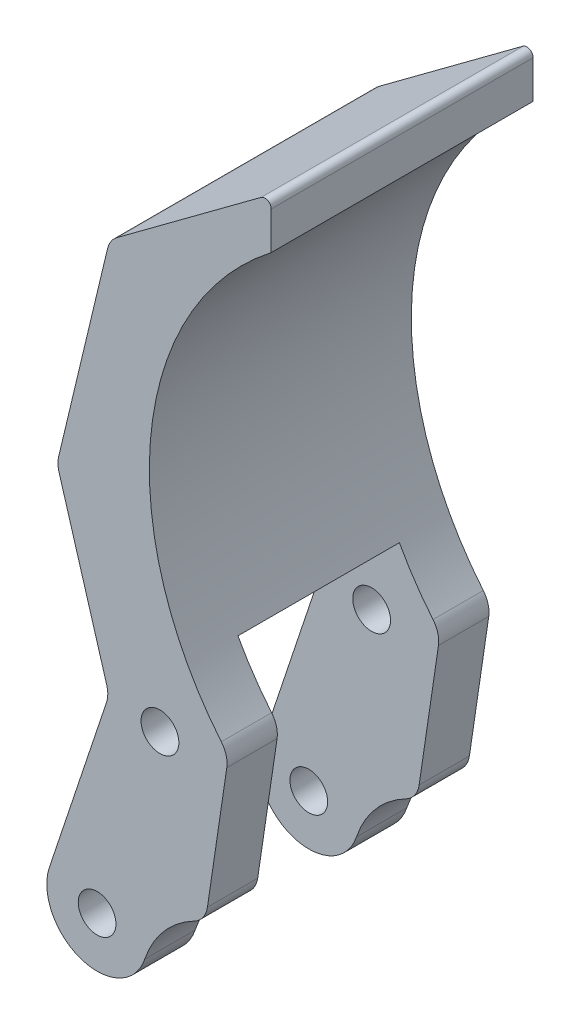
SolidWorks part; units mm, degrees
ref_plane "前视基准面" through (0, 0, 0) normal (0, 0, 1) x (1, 0, 0)
ref_plane "上视基准面" through (0, 0, 0) normal (0, 1, 0) x (1, 0, 0)
ref_plane "右视基准面" through (0, 0, 0) normal (1, 0, 0) x (0, 0, -1)
sketch "草图1" plane through (0, 0, 0) normal (0, 0, 1) x (1, 0, 0)
  line L1 (-44.759, 0) -> (37.6123, 0) construction
  line L2 (0, 0) -> (0, 68.6572) construction
  line L3 (15.4812, 24.7175) -> (6.2807, 1.4721) construction
  line L4 (22.9197, 21.7734) -> (13.7193, -1.4721) construction
  line L5 (22.9952, 24.5104) -> (15.4057, 21.9805) construction
  line L6 (8.8834, 38.4304) -> (10.4236, 28.044) construction
  line L8 (22.9952, 24.5104) -> (18.4512, 38.1424) construction
  line L9 (18.4316, 39.345) -> (22.233, 52.1252) construction
  line L10 (22.2613, 53.1601) -> (18.3728, 69.4382) construction
  line L11 (11.411, 39.3495) -> (2.2105, 16.1041) construction
  line L12 (16.9899, 37.1414) -> (7.7895, 13.8959) construction
  line L13 (17.619, 70.5799) -> (6.1506, 79.0862) construction
  line L14 (5.3527, 78.6846) -> (5.3527, 75.678) construction
  line L15 (-15.4812, 24.7175) -> (-6.2807, 1.4721) construction
  line L16 (-22.9197, 21.7734) -> (-13.7193, -1.4721) construction
  line L17 (-16.9899, 37.1414) -> (-7.7895, 13.8959) construction
  line L18 (-11.411, 39.3495) -> (-2.2105, 16.1041) construction
  line L19 (-8.8834, 38.4304) -> (-10.4236, 28.044)
  line L20 (-22.9952, 24.5104) -> (-18.4512, 38.1424)
  line L25 (-18.4316, 39.345) -> (-22.233, 52.1252)
  line L26 (-5, 15) -> (-10, 0) construction
  line L27 (5, 15) -> (10, 0) construction
  line L28 (14.2005, 38.2455) -> (19.2005, 23.2455) construction
  line L29 (-22.2613, 53.1601) -> (-18.3728, 69.4382)
  line L30 (-17.619, 70.5799) -> (-6.1506, 79.0862)
  line L31 (-5.3527, 78.6846) -> (-5.3527, 75.678)
  line L32 (-9.9581, 55.9149) -> (14.9371, 53.6276) construction
  circle A0 centre (-10, 0) radius 10 construction
  circle A4 centre (0, 55) radius 15 construction
  circle A5 centre (10, 0) radius 4 construction
  circle A6 centre (10, 0) radius 10 construction
  arc A14 (15.4057, 21.9805) -> (10.5848, 26.9564) centre (7.8163, 19.4507) ccw construction
  circle A16 centre (19.2005, 23.2455) radius 1.5 construction
  circle A17 centre (19.2005, 23.2455) radius 4 construction
  circle A18 centre (5, 15) radius 3 construction
  arc A19 (9.3195, 39.9972) -> (5.3527, 75.678) centre (-9.9581, 55.9149) ccw construction
  circle A20 centre (14.2005, 38.2455) radius 3 construction
  circle A21 centre (-10, 0) radius 4 construction
  circle A22 centre (-19.2005, 23.2455) radius 1.5
  arc A23 (-22.9952, 24.5104) -> (-15.4057, 21.9805) centre (-19.2005, 23.2455) ccw
  arc A24 (-15.4057, 21.9805) -> (-11.4848, 26.56) centre (-7.8163, 19.4507) cw
  circle A25 centre (-14.2005, 38.2455) radius 3 construction
  circle A26 centre (-5, 15) radius 3 construction
  circle A28 centre (-14.2005, 38.2455) radius 1.5
  circle A29 centre (-5, 15) radius 1.5 construction
  circle A30 centre (5, 15) radius 1.5 construction
  circle A31 centre (14.2005, 38.2455) radius 1.5 construction
  arc A33 (-11.4848, 26.56) -> (-10.4236, 28.044) centre (-12.4019, 28.3373) ccw
  arc A40 (6.1506, 79.0862) -> (5.3527, 78.6846) centre (5.8527, 78.6846) ccw construction
  arc A41 (11.4848, 26.56) -> (10.4236, 28.044) centre (12.4019, 28.3373) cw construction
  arc A42 (8.8834, 38.4304) -> (9.3195, 39.9972) centre (10.8617, 38.7237) cw construction
  arc A43 (-9.3195, 39.9972) -> (-5.3527, 75.678) centre (9.9581, 55.9149) cw
  arc A44 (18.4512, 38.1424) -> (18.4316, 39.345) centre (20.3486, 38.7748) cw construction
  arc A45 (22.233, 52.1252) -> (22.2613, 53.1601) centre (20.316, 52.6954) ccw construction
  arc A46 (18.3728, 69.4382) -> (17.619, 70.5799) centre (16.4275, 68.9735) ccw construction
  arc A47 (-6.1506, 79.0862) -> (-5.3527, 78.6846) centre (-5.8527, 78.6846) cw
  arc A48 (-8.8834, 38.4304) -> (-9.3195, 39.9972) centre (-10.8617, 38.7237) ccw
  arc A49 (-18.4512, 38.1424) -> (-18.4316, 39.345) centre (-20.3486, 38.7748) ccw
  arc A50 (-22.233, 52.1252) -> (-22.2613, 53.1601) centre (-20.316, 52.6954) cw
  arc A51 (-18.3728, 69.4382) -> (-17.619, 70.5799) centre (-16.4275, 68.9735) cw
  point P93 (5.3527, 79.678)
  point P96 (8.7498, 39.3313)
  point P99 (18.2518, 38.7406)
  point P102 (22.3858, 52.6388)
  point P105 (18.2036, 70.1462)
  point P109 (-5.3527, 79.678)
  point P112 (-8.7498, 39.3313)
  point P115 (-18.2518, 38.7406)
  point P118 (-10.5848, 26.9564)
  point P122 (-22.3858, 52.6388)
  point P125 (-18.2036, 70.1462)
  dimension "D1" = 30
  dimension "D3" = 20
  dimension "D4" = 25
  dimension "D5" = 8
  dimension "D6" = 3
  dimension "D7" = 2
  dimension "D8" = 8
  dimension "D13" = 25
  dimension "D20" = 140
  dimension "D21" = 6
  dimension "D27" = 3
  dimension "D29" = 0.5
  dimension "D28" = 16
  dimension "D30" = 2
  dimension "D31" = 55
  dimension "D14" = 4
  dimension "D12" = 10.5
  dimension "D18" = 150
  dimension "D10" = 0.5
  dimension "D26" = 2
  dimension "D9" = 11
  dimension "D11" = 15
  dimension "D15" = 10
  dimension "D16" = 145
  dimension "D17" = 14.5
  dimension "D19" = 18
  dimension "D22" = 5
  dimension "D23" = 15
  dimension "D24" = 25
  dimension "D25" = 4
extrude "凸台-拉伸1" add sketch "草图1" along normal blind 4
ref_plane "基准面1" through (0, 0, 0) normal (0, 0, -1) x (-1, 0, 0)
sketch "草图9" plane through (0, 0, 0) normal (0, 0, -1) x (-1, 0, 0)
  line L0 (18.4316, 39.345) -> (11.9955, 43.955)
  line L6 (8.8834, 38.4304) -> (10.4236, 28.044)
  line L7 (22.9952, 24.5104) -> (18.4512, 38.1424)
  line L8 (18.4316, 39.345) -> (22.233, 52.1252)
  line L9 (22.2613, 53.1601) -> (18.3728, 69.4382)
  line L10 (17.619, 70.5799) -> (6.1506, 79.0862)
  line L11 (5.3527, 78.6846) -> (5.3527, 75.678)
  line L14 (18.4316, 39.345) -> (22.233, 52.1252)
  line L15 (22.2613, 53.1601) -> (18.3728, 69.4382)
  line L16 (17.619, 70.5799) -> (6.1506, 79.0862)
  line L17 (5.3527, 78.6846) -> (5.3527, 75.678)
  arc A0 (5.3527, 75.678) -> (11.9955, 43.955) centre (-9.9581, 55.9149) cw
  arc A9 (9.3195, 39.9972) -> (5.3527, 75.678) centre (-9.9581, 55.9149) ccw
  arc A10 (9.3195, 39.9972) -> (8.8834, 38.4304) centre (10.8617, 38.7237) ccw
  arc A11 (10.4236, 28.044) -> (11.4848, 26.56) centre (12.4019, 28.3373) ccw
  arc A12 (15.4057, 21.9805) -> (11.4848, 26.56) centre (7.8163, 19.4507) ccw
  arc A13 (15.4057, 21.9805) -> (22.9952, 24.5104) centre (19.2005, 23.2455) ccw
  arc A14 (18.4316, 39.345) -> (18.4512, 38.1424) centre (20.3486, 38.7748) ccw
  arc A15 (22.233, 52.1252) -> (22.2613, 53.1601) centre (20.316, 52.6954) ccw
  arc A16 (18.3728, 69.4382) -> (17.619, 70.5799) centre (16.4275, 68.9735) ccw
  arc A17 (6.1506, 79.0862) -> (5.3527, 78.6846) centre (5.8527, 78.6846) ccw
  arc A24 (22.233, 52.1252) -> (22.2613, 53.1601) centre (20.316, 52.6954) ccw
  arc A25 (18.3728, 69.4382) -> (17.619, 70.5799) centre (16.4275, 68.9735) ccw
  arc A26 (6.1506, 79.0862) -> (5.3527, 78.6846) centre (5.8527, 78.6846) ccw
  dimension "D1" = 0
extrude "凸台-拉伸2" add sketch "草图9" against normal blind 20.84
ref_plane "基准面2" through (0, 0, 20.84) normal (0, 0, 1) x (1, 0, 0)
sketch "草图13" plane through (0, 0, 20.84) normal (0, 0, 1) x (1, 0, 0)
  line L3 (-11.9955, 43.955) -> (-18.4316, 39.345)
  line L4 (-18.4512, 38.1424) -> (-22.9952, 24.5104)
  line L5 (-10.4236, 28.044) -> (-8.8834, 38.4304)
  line L6 (-11.9955, 43.955) -> (-18.4316, 39.345)
  line L7 (-18.4512, 38.1424) -> (-22.9952, 24.5104)
  line L8 (-10.4236, 28.044) -> (-8.8834, 38.4304)
  arc A6 (-11.9955, 43.955) -> (-9.3195, 39.9972) centre (9.9581, 55.9149) ccw
  arc A7 (-18.4512, 38.1424) -> (-18.4316, 39.345) centre (-20.3486, 38.7748) ccw
  arc A8 (-22.9952, 24.5104) -> (-15.4057, 21.9805) centre (-19.2005, 23.2455) ccw
  arc A9 (-11.4848, 26.56) -> (-15.4057, 21.9805) centre (-7.8163, 19.4507) ccw
  arc A10 (-11.4848, 26.56) -> (-10.4236, 28.044) centre (-12.4019, 28.3373) ccw
  arc A11 (-8.8834, 38.4304) -> (-9.3195, 39.9972) centre (-10.8617, 38.7237) ccw
  arc A12 (-11.9955, 43.955) -> (-9.3195, 39.9972) centre (9.9581, 55.9149) ccw
  arc A13 (-18.4512, 38.1424) -> (-18.4316, 39.345) centre (-20.3486, 38.7748) ccw
  arc A14 (-22.9952, 24.5104) -> (-15.4057, 21.9805) centre (-19.2005, 23.2455) ccw
  arc A15 (-11.4848, 26.56) -> (-15.4057, 21.9805) centre (-7.8163, 19.4507) ccw
  arc A16 (-11.4848, 26.56) -> (-10.4236, 28.044) centre (-12.4019, 28.3373) ccw
  arc A17 (-8.8834, 38.4304) -> (-9.3195, 39.9972) centre (-10.8617, 38.7237) ccw
  dimension "D1" = 0
extrude "凸台-拉伸3" add sketch "草图13" against normal blind 4
sketch "草图14" plane through (0, 0, 0) normal (0, 0, -1) x (-1, 0, 0)
  circle A1 centre (12.7464, 38.6308) radius 0.0043
  circle A2 centre (14.2005, 38.2455) radius 1.5042
extrude "切除-拉伸1" cut sketch "草图14" against normal through all contours A1 A2 region at (-14.2005, 38.2455, 0)
sketch "草图15" plane through (0, 0, 0) normal (0, 0, -1) x (-1, 0, 0)
  circle A0 centre (19.2005, 23.2455) radius 1.5
extrude "切除-拉伸2" cut sketch "草图15" against normal through all
